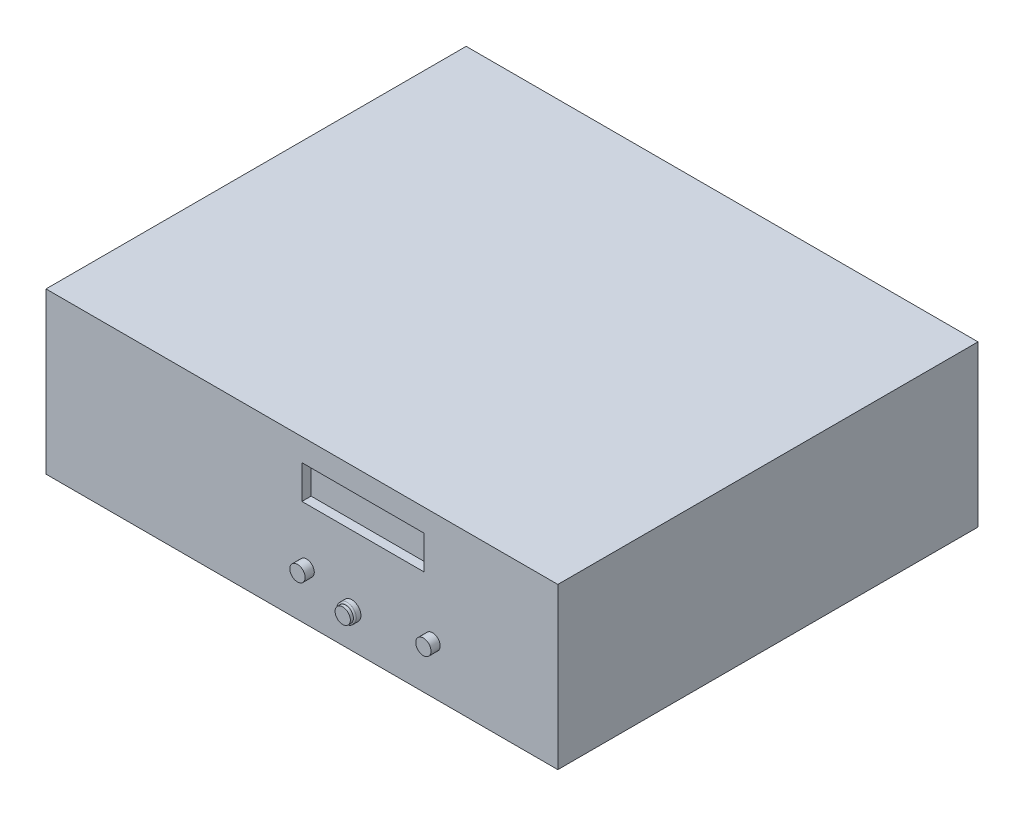
SolidWorks part; units mm, degrees
ref_plane "Front Plane" through (0, 0, 0) normal (0, 0, 1) x (1, 0, 0)
ref_plane "Top Plane" through (0, 0, 0) normal (0, 1, 0) x (1, 0, 0)
ref_plane "Right Plane" through (0, 0, 0) normal (1, 0, 0) x (0, 0, -1)
sketch "Sketch1" plane through (0, 0, 0) normal (0, 1, 0) x (1, 0, 0)
  line L1 (-212.725, -174.625) -> (212.725, -174.625)
  line L2 (-212.725, -174.625) -> (-212.725, 174.625)
  line L3 (-212.725, 174.625) -> (212.725, 174.625)
  line L4 (212.725, -174.625) -> (212.725, 174.625)
  line L5 (-212.725, -174.625) -> (212.725, 174.625) construction
  line L6 (-212.725, 174.625) -> (212.725, -174.625) construction
  point P0 (0, 0)
  dimension "D1" = 425.45
  dimension "D2" = 349.25
extrude "Boss-Extrude1" add sketch "Sketch1" along normal blind 133.35
sketch "Sketch3" plane through (0, 0, 174.625) normal (0, 0, 1) x (1, 0, 0)
  line L1 (0, 86.7356) -> (101.6111, 86.7356)
  line L2 (0, 86.7356) -> (0, 114.6459)
  line L3 (0, 114.6459) -> (101.6111, 114.6459)
  line L4 (101.6111, 86.7356) -> (101.6111, 114.6459)
extrude "Cut-Extrude1" cut sketch "Sketch3" against normal blind 7.62
sketch "Sketch4" plane through (0, 0, 174.625) normal (0, 0, 1) x (1, 0, 0)
  circle A0 centre (3.9249, 40.8754) radius 6.35
  dimension "D1" = 12.7
extrude "Boss-Extrude2" add sketch "Sketch4" along normal blind 7.62
sketch "Sketch5" plane through (0, 0, 174.625) normal (0, 0, 1) x (1, 0, 0)
  circle A0 centre (41.4294, 29.1007) radius 7.62
  dimension "D1" = 15.24
extrude "Boss-Extrude3" add sketch "Sketch5" along normal blind 5.08
fillet "Fillet1" radius 1.27 1 edges at (49.0494, 29.1007, 179.705) conic radius 0.254
sketch "Sketch7" plane through (0, 0, 179.705) normal (0, 0, 1) x (1, 0, 0)
  circle A0 centre (41.5366, 29.0449) radius 6.35
  dimension "D1" = 12.7
extrude "Boss-Extrude4" add sketch "Sketch7" along normal blind 2.54
sketch "Sketch8" plane through (0, 0, 174.625) normal (0, 0, 1) x (1, 0, 0)
  circle A0 centre (108.5887, 40.1644) radius 6.35
  dimension "D1" = 12.7
extrude "Boss-Extrude5" add sketch "Sketch8" along normal blind 7.62
